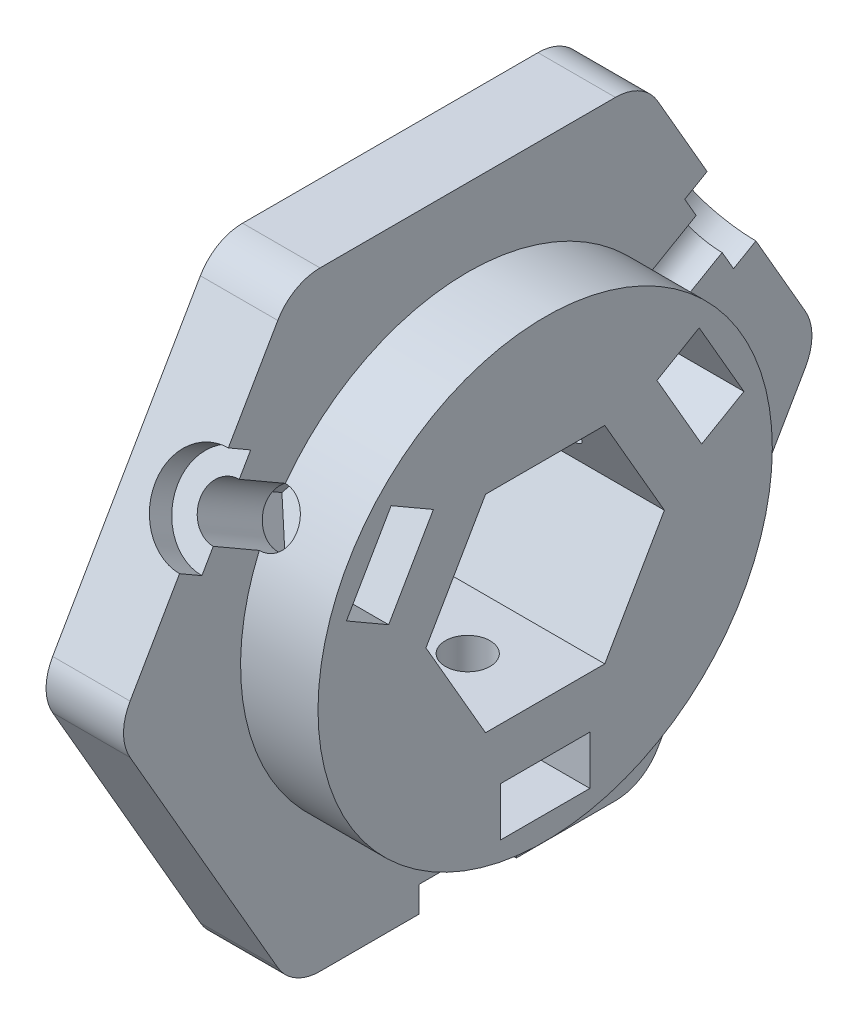
SolidWorks part; units mm, degrees
ref_plane "Front Plane" through (0, 0, 0) normal (0, 0, 1) x (1, 0, 0)
ref_plane "Top Plane" through (0, 0, 0) normal (0, 1, 0) x (1, 0, 0)
ref_plane "Right Plane" through (0, 0, 0) normal (1, 0, 0) x (0, 0, -1)
sketch "Sketch1" plane through (0, 0, 0) normal (1, 0, 0) x (0, 0, -1)
  line L1 (-10.8152, 18.7325) -> (-21.6304, 0)
  line L2 (-21.6304, 0) -> (-10.8152, -18.7325)
  line L3 (-10.8152, -18.7325) -> (10.8152, -18.7325)
  line L4 (10.8152, -18.7325) -> (21.6304, 0)
  line L5 (21.6304, 0) -> (10.8152, 18.7325)
  line L6 (10.8152, 18.7325) -> (-10.8152, 18.7325)
  circle A0 centre (0, 0) radius 18.7325 construction
  dimension "D1" = 37.465
extrude "Boss-Extrude1" add sketch "Sketch1" along normal blind 4.7625
sketch "Sketch2" plane through (4.7625, 0, 0) normal (1, 0, 0) x (0, 0, -1)
  circle A0 centre (0, 0) radius 13.97
  dimension "D1" = 27.94
extrude "Boss-Extrude2" add sketch "Sketch2" along normal blind 4.7625
sketch "Sketch3" plane through (0, -18.7325, 0) normal (0, -1, 0) x (1, 0, 0)
  line L0 (4.7625, 10.8152) -> (4.7625, -10.8152) construction
  circle A0 centre (4.7625, 0) radius 3
  dimension "D1" = 6
extrude "Cut-Extrude1" cut sketch "Sketch3" against normal blind 1.5875
ref_axis "Axis1" through (9.525, 0, 0) along (-1, 0, 0)
ref_plane "Plane1" through (0, 0, 0) normal (0, -1, 0) x (-1, 0, 0)
sketch "Sketch6" plane through (0, 0, 0) normal (0, -1, 0) x (-1, 0, 0)
  line L0 (-6.3502, 2.75) -> (-9.525, 2.75)
  line L1 (-7.9379, 0) -> (-6.3502, -2.75) construction
  line L2 (-6.3502, -2.75) -> (-3.1748, -2.75)
  line L3 (-3.1748, -2.75) -> (-1.5871, 0)
  line L4 (-1.5871, 0) -> (-3.1748, 2.75)
  line L5 (-3.1748, 2.75) -> (-6.3502, 2.75)
  line L6 (-6.3502, 2.75) -> (-7.9379, 0) construction
  line L7 (-9.525, 13.97) -> (-9.525, -13.97) construction
  line L8 (-9.525, 2.75) -> (-9.525, -2.75)
  line L9 (-9.525, -2.75) -> (-6.3502, -2.75)
  circle A0 centre (-4.7625, 0) radius 2.75 construction
  arc A3 (-4.7625, -3) -> (-4.7625, 3) centre (-4.7625, 0) ccw construction
  point P13 (0, 0)
  dimension "D1" = 5.5
extrude "Cut-Extrude4" cut sketch "Sketch6" along normal blind 3 from offset 9.525
sketch "Sketch4" plane through (0, -17.145, 0) normal (0, -1, 0) x (1, 0, 0)
  line L0 (4.7625, 3) -> (4.7625, -3) construction
  circle A0 centre (4.7625, 0) radius 1.6
  dimension "D1" = 3.2
extrude "Cut-Extrude2" cut sketch "Sketch4" against normal up to surface (7.62 mm away) up to face at (5.3973, -9.525, 0)
sketch "Sketch5" plane through (0, -17.145, 0) normal (0, -1, 0) x (1, 0, 0)
  circle A0 centre (4.7625, 0) radius 1.375
  dimension "D1" = 2.75
extrude "Cut-Extrude3" cut sketch "Sketch5" against normal blind 12.7
pattern_circular "CirPattern3" count 3 over 360 about axis through (9.525, 0, 0) along (-1, 0, 0) of "Cut-Extrude3", "Cut-Extrude2", "Cut-Extrude4", "Cut-Extrude1"
fillet "Fillet1" radius 3 6 edges at (2.3813, 18.7325, 10.8152) (2.3813, 0, 21.6304) (2.3813, -18.7325, 10.8152) (2.3813, 18.7325, -10.8152) (2.3813, 0, -21.6304) (2.3813, -18.7325, -10.8152)
sketch "Sketch7" plane through (9.525, 0, 0) normal (1, 0, 0) x (0, 0, -1)
  circle A0 centre (0, 0) radius 4.7625
  dimension "D1" = 9.525
extrude "Cut-Extrude5" cut sketch "Sketch7" against normal through all
sketch "Sketch8" plane through (9.525, 0, 0) normal (1, 0, 0) x (0, 0, -1)
  line L1 (7.3323, 0) -> (3.6662, 6.35)
  line L2 (3.6662, 6.35) -> (-3.6662, 6.35)
  line L3 (-3.6662, 6.35) -> (-7.3323, 0)
  line L4 (-7.3323, 0) -> (-3.6662, -6.35)
  line L5 (-3.6662, -6.35) -> (3.6662, -6.35)
  line L6 (3.6662, -6.35) -> (7.3323, 0)
  circle A0 centre (0, 0) radius 6.35 construction
  dimension "D1" = 12.7
extrude "Cut-Extrude6" cut sketch "Sketch8" against normal through all
